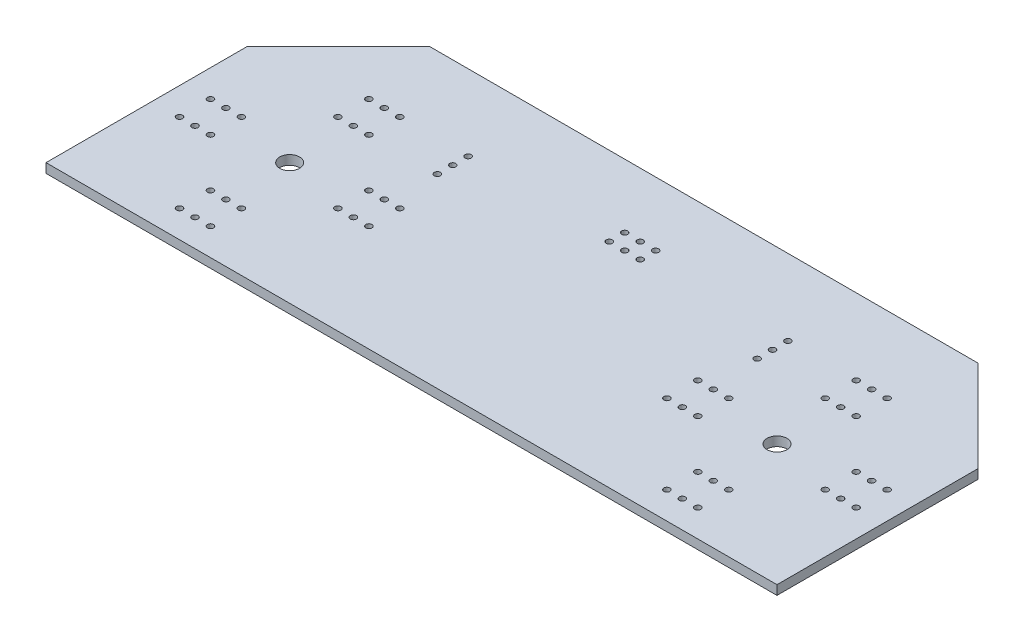
SolidWorks part; units mm, degrees
ref_plane "Front Plane" through (0, 0, 0) normal (0, 0, 1) x (1, 0, 0)
ref_plane "Top Plane" through (0, 0, 0) normal (0, 1, 0) x (1, 0, 0)
ref_plane "Right Plane" through (0, 0, 0) normal (1, 0, 0) x (0, 0, -1)
sketch "Sketch1" plane through (0, 0, 0) normal (0, 1, 0) x (1, 0, 0)
  line L0 (0, 0) -> (0, 13) construction
  line L1 (-60, -20) -> (60, -20)
  line L2 (-60, -20) -> (-60, 28)
  line L3 (-60, 28) -> (60, 28)
  line L4 (60, -20) -> (60, 28)
  line L5 (0, 0) -> (60, 28) construction
  line L6 (-60, 28) -> (0, 0) construction
  line L11 (0, 13) -> (0, 28) construction
  point P0 (0, 0)
  dimension "D1" = 120
  dimension "D2" = 28
  dimension "D6" = 20
extrude "Boss-Extrude1" add sketch "Sketch1" along normal blind 1.53
sketch "Sketch2" plane through (0, 1.53, 0) normal (0, 1, 0) x (1, 0, 0)
  line L0 (-55.54, 2.54) -> (-53, 2.54) construction
  line L1 (-53, 2.54) -> (-50.46, 2.54) construction
  line L2 (-53, 2.54) -> (-53, -2.54) construction
  line L3 (-53, -2.54) -> (-50.46, -2.54) construction
  line L4 (-53, -2.54) -> (-55.54, -2.54) construction
  line L5 (-53, 0) -> (-27, 0) construction
  line L6 (-29.54, 2.54) -> (-27, 2.54) construction
  line L7 (-27, 2.54) -> (-24.46, 2.54) construction
  line L8 (-27, 2.54) -> (-27, -2.54) construction
  line L9 (-27, -2.54) -> (-24.46, -2.54) construction
  line L10 (-27, -2.54) -> (-29.54, -2.54) construction
  line L11 (-42.54, 15.54) -> (-40, 15.54) construction
  line L12 (-40, 15.54) -> (-37.46, 15.54) construction
  line L13 (-40, 15.54) -> (-40, 10.46) construction
  line L14 (-40, 10.46) -> (-37.46, 10.46) construction
  line L15 (-40, 10.46) -> (-42.54, 10.46) construction
  line L16 (-42.54, -10.46) -> (-40, -10.46) construction
  line L17 (-40, -10.46) -> (-37.46, -10.46) construction
  line L18 (-40, -10.46) -> (-40, -15.54) construction
  line L19 (-40, -15.54) -> (-37.46, -15.54) construction
  line L20 (-40, -15.54) -> (-42.54, -15.54) construction
  line L21 (-40, -13) -> (-40, 0) construction
  line L22 (-40, 0) -> (-40, 13) construction
  line L23 (-27, 0) -> (0, 0) construction
  circle A0 centre (-55.54, 2.54) radius 0.5
  circle A1 centre (-53, 2.54) radius 0.5
  circle A2 centre (-50.46, 2.54) radius 0.5
  circle A3 centre (-55.54, -2.54) radius 0.5
  circle A4 centre (-53, -2.54) radius 0.5
  circle A5 centre (-50.46, -2.54) radius 0.5
  circle A6 centre (-29.54, 2.54) radius 0.5
  circle A7 centre (-27, 2.54) radius 0.5
  circle A8 centre (-24.46, 2.54) radius 0.5
  circle A9 centre (-29.54, -2.54) radius 0.5
  circle A10 centre (-27, -2.54) radius 0.5
  circle A11 centre (-24.46, -2.54) radius 0.5
  circle A12 centre (-42.54, 15.54) radius 0.5
  circle A13 centre (-40, 15.54) radius 0.5
  circle A14 centre (-37.46, 15.54) radius 0.5
  circle A15 centre (-42.54, 10.46) radius 0.5
  circle A16 centre (-40, 10.46) radius 0.5
  circle A17 centre (-37.46, 10.46) radius 0.5
  circle A18 centre (-42.54, -10.46) radius 0.5
  circle A19 centre (-40, -10.46) radius 0.5
  circle A20 centre (-37.46, -10.46) radius 0.5
  circle A21 centre (-42.54, -15.54) radius 0.5
  circle A22 centre (-40, -15.54) radius 0.5
  circle A23 centre (-37.46, -15.54) radius 0.5
  circle A24 centre (-40, 0) radius 1.625
  point P15 (-27, 0)
  dimension "D1" = 1
  dimension "D7" = 3.25
  dimension "D2" = 2.54
  dimension "D3" = 5.08
  dimension "D4" = 26
  dimension "D5" = 26
  dimension "D6" = 40
extrude "Cut-Extrude1" cut sketch "Sketch2" against normal through all
mirror "Mirror1" about plane through (0, 0, 0) normal (1, 0, 0) of "Cut-Extrude1"
sketch "Sketch5" plane through (0, 1.53, 0) normal (0, 1, 0) x (1, 0, 0)
  line L0 (-2.54, 17.54) -> (0, 17.54) construction
  line L1 (0, 17.54) -> (2.54, 17.54) construction
  line L2 (0, 17.54) -> (0, 15) construction
  line L3 (0, 15) -> (2.54, 15) construction
  line L4 (0, 15) -> (-2.54, 15) construction
  line L5 (0, 0) -> (0, 15) construction
  circle A0 centre (-2.54, 17.54) radius 0.5
  circle A1 centre (0, 17.54) radius 0.5
  circle A2 centre (2.54, 17.54) radius 0.5
  circle A3 centre (-2.54, 15) radius 0.5
  circle A4 centre (0, 15) radius 0.5
  circle A5 centre (2.54, 15) radius 0.5
  dimension "D1" = 2.54
  dimension "D2" = 2.54
  dimension "D3" = 15
extrude "Cut-Extrude2" cut sketch "Sketch5" against normal through all
sketch "Sketch6" plane through (0, 1.53, 0) normal (0, 1, 0) x (1, 0, 0)
  line L0 (-45, 28) -> (-60, 13)
  line L1 (60, 28) -> (-60, 28) construction
  line L2 (-60, 28) -> (-60, -20) construction
  line L12 (60, -20) -> (60, 28) construction
  line L13 (60, -14) -> (60, 13)
  line L14 (60, 13) -> (45, 28)
  line L16 (0, 0) -> (0, -18) construction
  line L17 (0, 0) -> (0, 28) construction
  line L18 (-60, 13) -> (-60, 28)
  line L23 (-60, 28) -> (-45, 28)
  line L24 (45, 28) -> (60, 28)
  line L25 (60, 28) -> (60, 13)
  dimension "D1" = 45
  dimension "D2" = 45
  dimension "D3" = 90
extrude "Cut-Extrude4" cut sketch "Sketch6" against normal through all contours L23 L18 L0 | L25 L24 L14 region at (-55, 1.53, -23) region at (55, 1.53, -23)
sketch "Sketch7" plane through (0, 1.53, 0) normal (0, 1, 0) x (1, 0, 0)
  line L0 (-26.25, 15.54) -> (-26.25, 13.02) construction
  line L1 (-26.25, 13.02) -> (-26.25, 10.5) construction
  line L2 (-26.25, 10.5) -> (-26.25, 0) construction
  line L3 (-26.25, 0) -> (0, 0) construction
  line L4 (0, 0.353) -> (0, 11.8498) construction
  line L5 (26.25, 13.02) -> (26.25, 10.5) construction
  line L6 (26.25, 15.54) -> (26.25, 13.02) construction
  circle A0 centre (-26.25, 15.54) radius 0.5
  circle A1 centre (-26.25, 13.02) radius 0.5
  circle A2 centre (-26.25, 10.5) radius 0.5
  circle A3 centre (26.25, 10.5) radius 0.5
  circle A4 centre (26.25, 13.02) radius 0.5
  circle A5 centre (26.25, 15.54) radius 0.5
  dimension "D1" = 1
  dimension "D2" = 5.04
  dimension "D3" = 26.25
  dimension "D4" = 10.5
extrude "Cut-Extrude5" cut sketch "Sketch7" against normal through all
